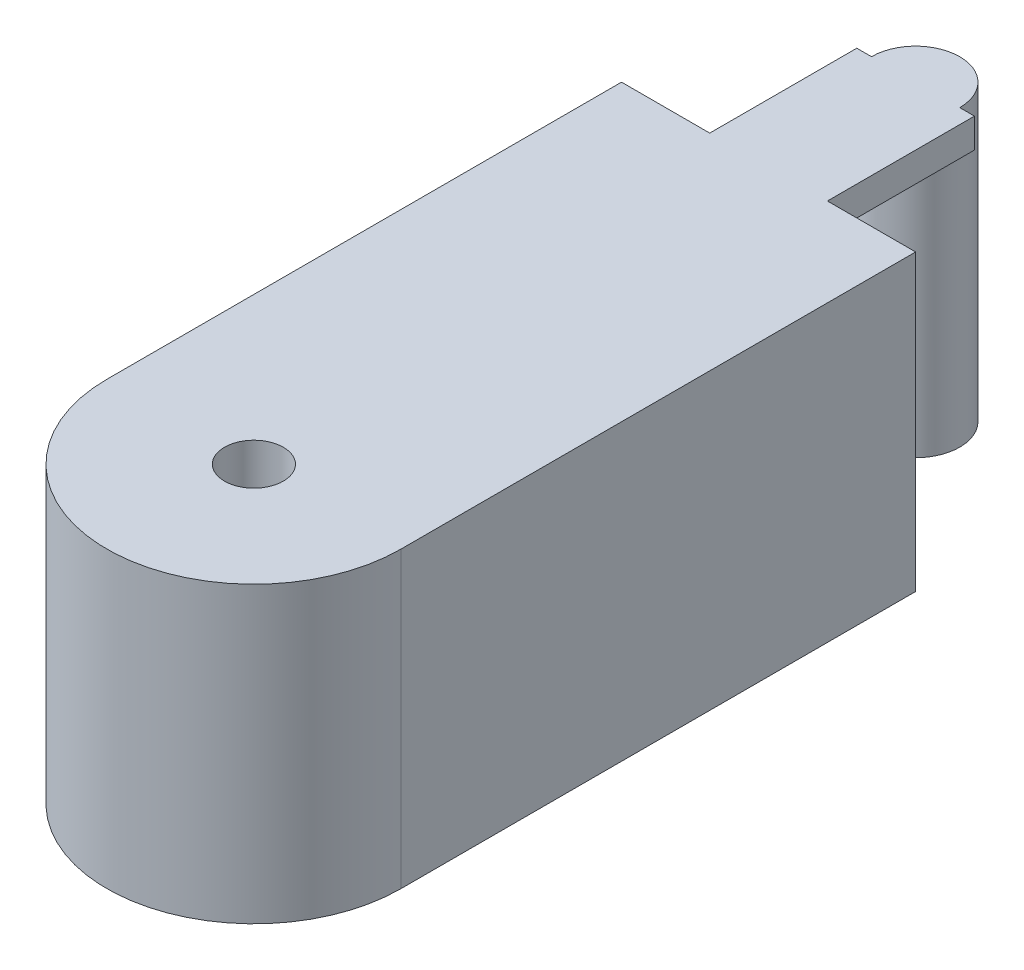
SolidWorks part; units mm, degrees
ref_plane "Front Plane" through (0, 0, 0) normal (0, 0, 1) x (1, 0, 0)
ref_plane "Top Plane" through (0, 0, 0) normal (0, 1, 0) x (1, 0, 0)
ref_plane "Right Plane" through (0, 0, 0) normal (1, 0, 0) x (0, 0, -1)
sketch "Sketch2" plane through (0, 0, 0) normal (0, 1, 0) x (1, 0, 0)
  circle A0 centre (0, 0) radius 50
  circle A1 centre (0, 0) radius 10
  dimension "D1" = 100
  dimension "D2" = 20
extrude "Boss-Extrude1" add sketch "Sketch2" along normal blind 100
sketch "Sketch3" plane through (0, 100, 0) normal (0, 1, 0) x (1, 0, 0)
  line L0 (50, 0) -> (50, 175)
  line L1 (50, 175) -> (-50, 175)
  line L2 (-50, 0) -> (-50, 175)
  line L3 (-50, 0) -> (50, 0)
  arc A0 (-50, 0) -> (50, 0) centre (0, 0) ccw
  circle M6 centre (0, 0) radius 50
  dimension "D1" = 50
  dimension "D2" = 225
  dimension "D3" = 100
extrude "Boss-Extrude2" add sketch "Sketch3" against normal up to vertex (100 mm away) contours L2 L0 L1 M6 region at (0, 100, -106.6762) up to point (0, 0, 0)
sketch "Sketch4" plane through (0, 100, 0) normal (0, 1, 0) x (1, 0, 0)
  line L0 (50, 175) -> (-50, 175) construction
  line L1 (20, 175) -> (-20, 175)
  line L2 (20, 175) -> (20, 225)
  line L3 (20, 225) -> (-20, 225)
  line L4 (-20, 175) -> (-20, 225)
  circle A0 centre (0, 225) radius 15
  point P6 (0, 175)
  line M7 (50, 175) -> (-50, 175)
  dimension "D1" = 40
  dimension "D2" = 30
  dimension "D3" = 50
extrude "Boss-Extrude3" add sketch "Sketch4" against normal blind 10 contours A0 L3 L4 L2 M7 region at (0, 100, -196.0003)
extrude "Boss-Extrude4" add sketch "Sketch4<3>" against normal blind 100 contours L3 A0 | L3 A0 region at (0, 100, -218.6338) region at (0, 100, -231.3662)
sketch "Sketch4<3>" plane through (0, 100, 0) normal (0, 1, 0) x (1, 0, 0) same geometry as "Sketch4"
